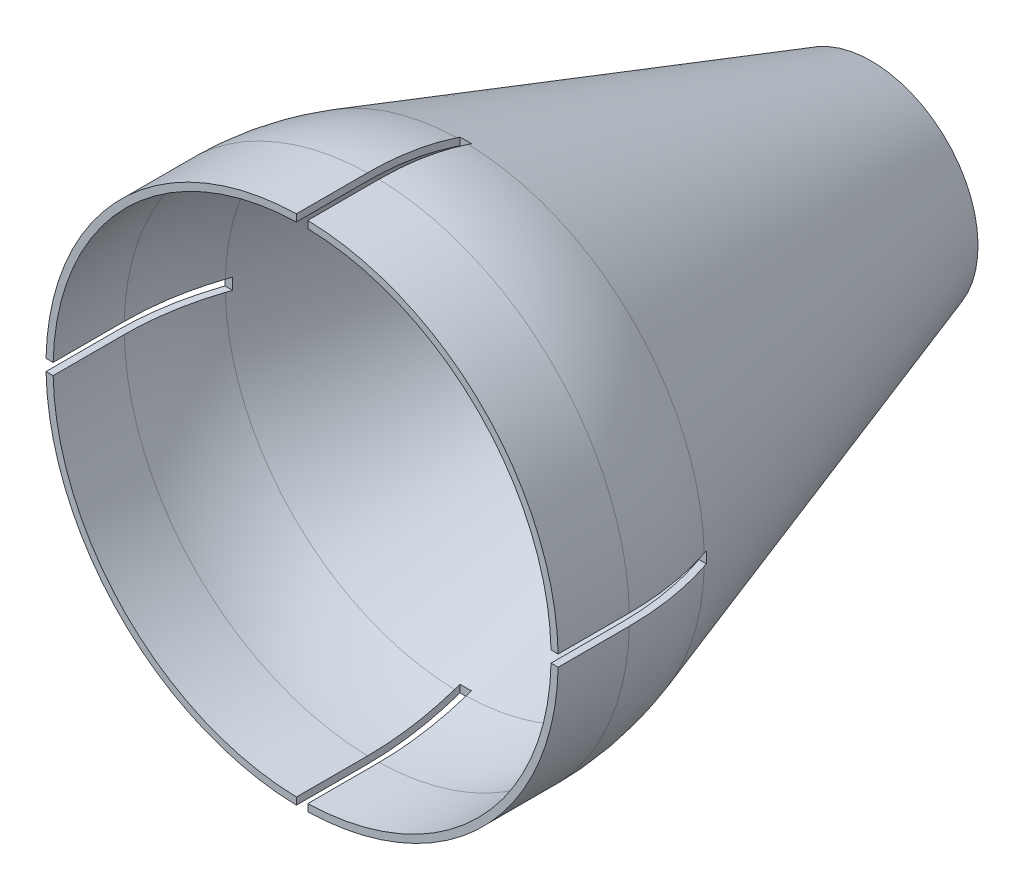
SolidWorks part; units mm, degrees
material "AISI Type 316L stainless steel"
ref_plane "Front Plane" through (0, 0, 0) normal (0, 0, 1) x (1, 0, 0)
ref_plane "Top Plane" through (0, 0, 0) normal (0, 1, 0) x (1, 0, 0)
ref_plane "Right Plane" through (0, 0, 0) normal (1, 0, 0) x (0, 0, -1)
sketch "Sketch1" plane through (0, 0, 0) normal (1, 0, 0) x (0, 0, -1)
  line L0 (0, 0) -> (-38.3311, 0) construction
  line L1 (0, 7.5) -> (-28.726, 16.9904)
  line L2 (-35, 18) -> (-40, 18)
  arc A0 (-28.726, 16.9904) -> (-35, 18) centre (-35, -2) ccw
  dimension "D1" = 20
  dimension "D2" = 15
  dimension "D3" = 36
  dimension "D4" = 5
  dimension "D5" = 40
revolve "Revolve-Thin1" add sketch "Sketch1" angle 360 about L0 wall 0.5
sketch "Sketch2" plane through (0, 0, 0) normal (0, 1, 0) x (1, 0, 0)
  line L0 (0, 0) -> (0, -42.1626) construction
  line L1 (-18, -40) -> (18, -40) construction
  line L2 (-0.4, -40) -> (0.4, -40)
  line L3 (-0.4, -40) -> (-0.4, -28.5)
  line L4 (-0.4, -28.5) -> (0.4, -28.5)
  line L5 (0.4, -40) -> (0.4, -28.5)
  dimension "D1" = 0.8
  dimension "D2" = 11.5
extrude "Cut-Extrude1" cut sketch "Sketch2" against normal through all
ref_axis "Axis1" through (0, 0, 44.2707) along (0, 0, -1)
pattern_circular "CirPattern1" count 4 over 360 about axis through (0, 0, 44.2707) along (0, 0, -1) of "Cut-Extrude1"
